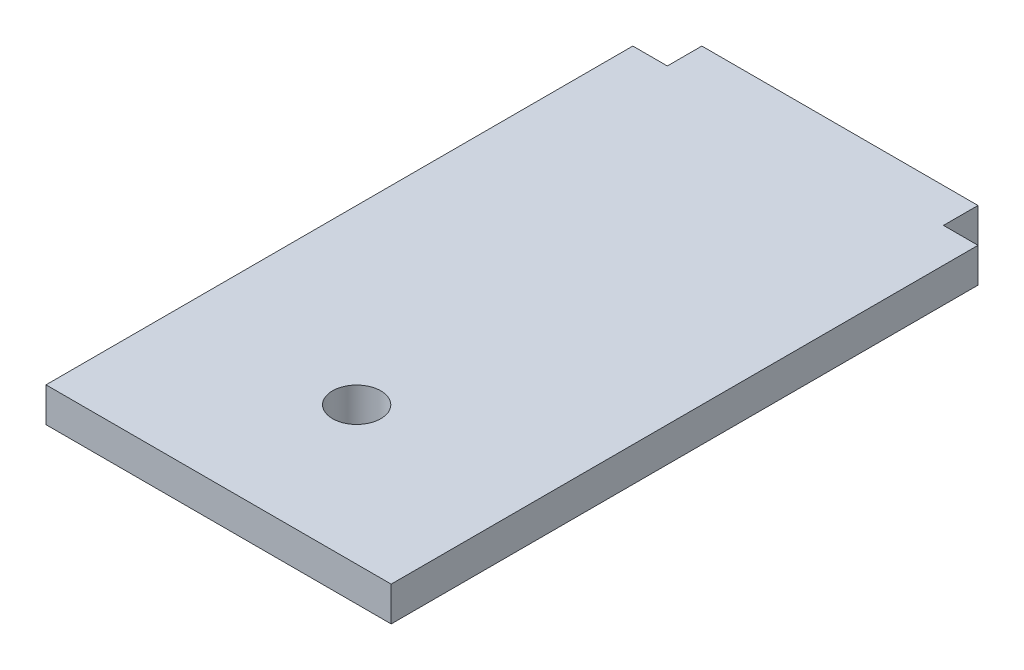
SolidWorks part; units mm, degrees
ref_plane "Front Plane" through (0, 0, 0) normal (0, 0, 1) x (1, 0, 0)
ref_plane "Top Plane" through (0, 0, 0) normal (0, 1, 0) x (1, 0, 0)
ref_plane "Right Plane" through (0, 0, 0) normal (1, 0, 0) x (0, 0, -1)
sketch "Sketch1" plane through (0, 0, 0) normal (0, 1, 0) x (1, 0, 0)
  line L0 (0, 85) -> (5, 85)
  line L1 (0, 0) -> (50, 0)
  line L2 (0, 0) -> (0, 85)
  line L3 (5, 90) -> (45, 90)
  line L4 (50, 0) -> (50, 85)
  line L5 (5, 90) -> (5, 85)
  line L6 (50, 85) -> (45, 85)
  line L7 (45, 85) -> (45, 90)
  circle A0 centre (25, 20) radius 3.5
  point P10 (25, 0)
  dimension "D6" = 7
  dimension "D1" = 85
  dimension "D2" = 5
  dimension "D3" = 5
  dimension "D4" = 5
  dimension "D5" = 50
  dimension "D7" = 20
extrude "Boss-Extrude1" add sketch "Sketch1" along normal blind 5
